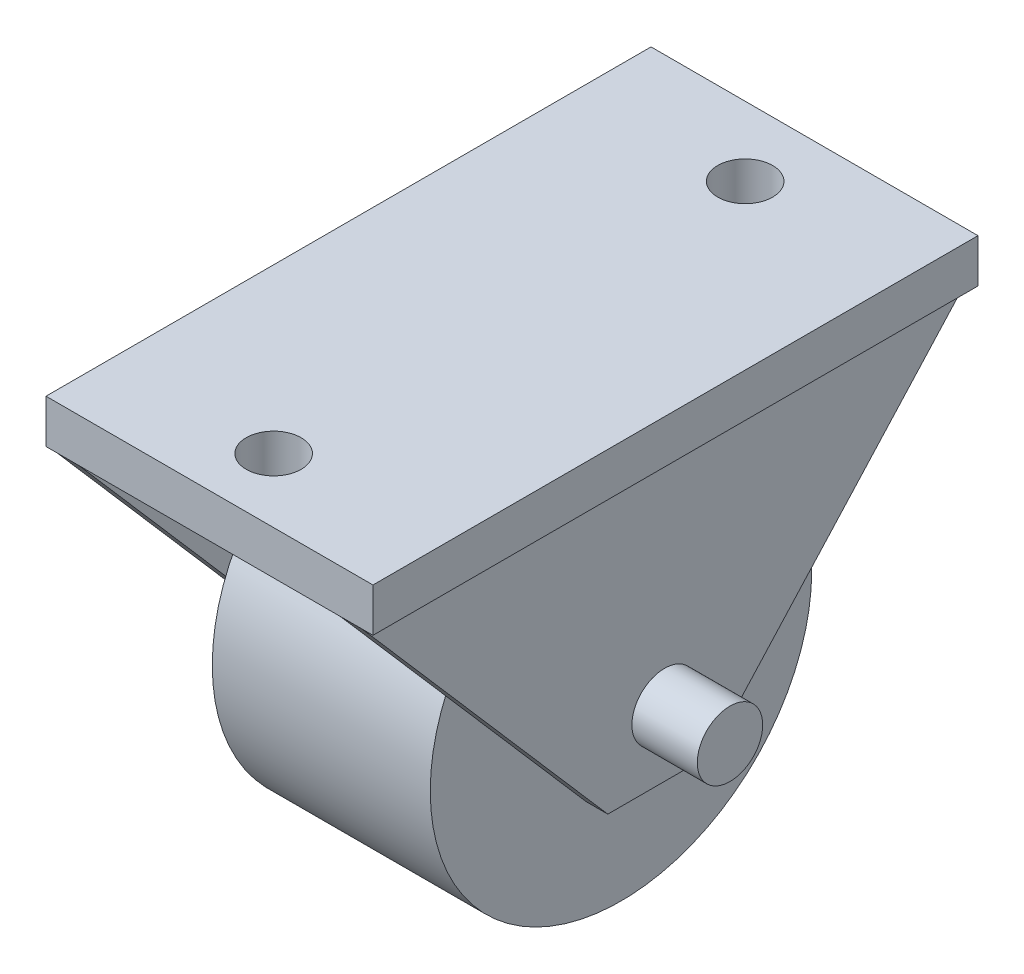
SolidWorks part; units mm, degrees
ref_plane "Front Plane" through (0, 0, 0) normal (0, 0, 1) x (1, 0, 0)
ref_plane "Top Plane" through (0, 0, 0) normal (0, 1, 0) x (1, 0, 0)
ref_plane "Right Plane" through (0, 0, 0) normal (1, 0, 0) x (0, 0, -1)
sketch "Sketch1" plane through (0, 0, 0) normal (1, 0, 0) x (0, 0, -1)
  circle A0 centre (0, 0) radius 8.75
  circle A1 centre (0, 0) radius 1.5
extrude "Boss-Extrude1" add sketch "Sketch1" along normal mid plane 10
extrude "Boss-Extrude2" add sketch "Sketch1<2>" against normal mid plane 20 contours A1 region at (0, 0, 0)
sketch "Sketch1<2>" plane through (0, 0, 0) normal (1, 0, 0) x (0, 0, -1) same geometry as "Sketch1"
sketch "Sketch2" plane through (0, 0, 0) normal (0, 1, 0) x (1, 0, 0)
  line L1 (-7.5, -13.8779) -> (7.5, -13.8779)
  line L2 (-7.5, -13.8779) -> (-7.5, 13.8779)
  line L3 (-7.5, 13.8779) -> (7.5, 13.8779)
  line L4 (7.5, -13.8779) -> (7.5, 13.8779)
  line L5 (-7.5, -13.8779) -> (7.5, 13.8779) construction
  line L6 (-7.5, 13.8779) -> (7.5, -13.8779) construction
  circle A0 centre (0, 10.6964) radius 1.2593
  circle A1 centre (0, -10.9341) radius 1.2593
  point P0 (0, 0)
  point P10 (1.3496, -5.3699)
  point P11 (0, -10.9341)
  point P12 (0, 0)
  point P13 (0, 0)
extrude "Boss-Extrude3" add sketch "Sketch2" along normal blind 2 from offset 10 separate body
sketch "Sketch3" plane through (0, 0, 0) normal (1, 0, 0) x (0, 0, -1)
  line L0 (-13.8779, 10) -> (-2.6051, -2.9914)
  line L1 (-13.8779, 10) -> (13.8779, 10) construction
  line L2 (-13.8779, 12) -> (-13.8779, 10) construction
  line L3 (-2.6051, -2.9914) -> (2.0977, -2.9914)
  line L4 (2.0977, -2.9914) -> (13.8779, 10)
  line L5 (13.8779, 10) -> (-13.8779, 10)
extrude "Boss-Extrude4" add sketch "Sketch3" along normal blind 1 from offset 6
extrude "Boss-Extrude5" add sketch "Sketch3<2>" against normal blind 1 from offset 6
sketch "Sketch3<2>" plane through (0, 0, 0) normal (1, 0, 0) x (0, 0, -1) same geometry as "Sketch3"
